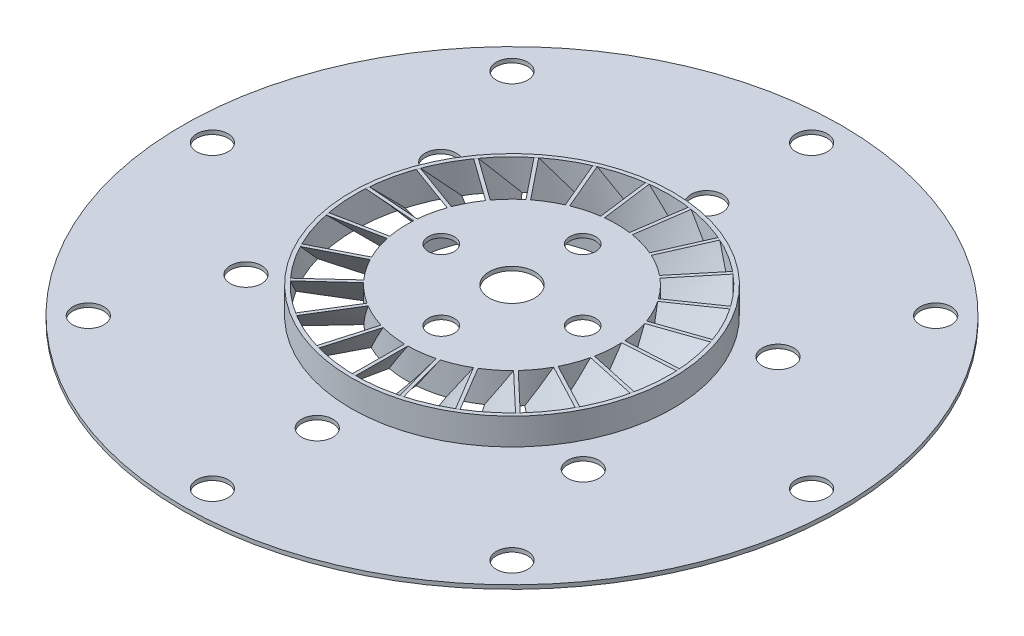
SolidWorks part; units mm, degrees
ref_plane "Front Plane" through (0, 0, 0) normal (0, 0, 1) x (1, 0, 0)
ref_plane "Top Plane" through (0, 0, 0) normal (0, 1, 0) x (1, 0, 0)
ref_plane "Right Plane" through (0, 0, 0) normal (1, 0, 0) x (0, 0, -1)
sketch "Sketch1" plane through (0, 0, 0) normal (0, 1, 0) x (1, 0, 0)
  circle A0 centre (0, 0) radius 33.25
  circle A1 centre (0, 0) radius 34.0882
  circle A2 centre (0, 0) radius 69.85
  circle A3 centre (0, 0) radius 22.25
  circle A4 centre (0, 0) radius 21.4118
  dimension "D1" = 66.5
  dimension "D2" = 0.8382
  dimension "D3" = 139.7
  dimension "D4" = 44.5
  dimension "D5" = 0.8382
extrude "Boss-Extrude1" add sketch "Sketch1" along normal blind 6.5 contours A1 A0 region at (-33.9918, 0, 0)
extrude "Boss-Extrude2" add sketch "Sketch1<3>" along normal blind 0.8382 contours A2 A1 region at (-67.8743, 0, 0)
sketch "Sketch1<3>" plane through (0, 0, 0) normal (0, 1, 0) x (1, 0, 0) same geometry as "Sketch1"
extrude "Boss-Extrude3" add sketch "Sketch1<4>" along normal blind 6.5 separate body contours A3 A4 region at (-21.6207, 0, 0)
sketch "Sketch1<4>" plane through (0, 0, 0) normal (0, 1, 0) x (1, 0, 0) same geometry as "Sketch1"
extrude "Boss-Extrude4" add sketch "Sketch1<5>" along normal blind 0.7 contours A4 region at (0, 0, 0)
sketch "Sketch1<5>" plane through (0, 0, 0) normal (0, 1, 0) x (1, 0, 0) same geometry as "Sketch1"
sketch "Sketch2" plane through (0, 0, 0) normal (0, -1, 0) x (1, 0, 0)
  line L0 (-31.9208, 9.3073) -> (-21.3278, 6.3393)
  line L1 (-33.2482, 0.35) -> (-22.2472, 0.35)
  line L2 (-33.2482, -0.35) -> (-22.2472, -0.35)
  line L3 (-32.1097, 8.6332) -> (-21.5167, 5.6652)
  line L4 (-28.226, 17.5743) -> (-18.8266, 11.8584)
  line L5 (-28.5897, 16.9762) -> (-19.1903, 11.2603)
  line L6 (-22.4378, 24.5378) -> (-14.9291, 16.498)
  line L7 (-22.9494, 24.0601) -> (-15.4407, 16.0202)
  line L8 (-14.9856, 29.6816) -> (-9.9244, 19.914)
  line L9 (-15.6071, 29.3595) -> (-10.5459, 19.592)
  line L10 (-6.4219, 32.624) -> (-4.1837, 21.8531)
  line L11 (-7.1072, 32.4815) -> (-4.869, 21.7107)
  line L12 (2.6181, 33.1468) -> (1.8674, 22.1715)
  line L13 (1.9198, 33.1945) -> (1.169, 22.2193)
  line L14 (11.4639, 31.2112) -> (7.7799, 20.8455)
  line L15 (10.8043, 31.4456) -> (7.1204, 21.0799)
  line L16 (19.4595, 26.9609) -> (13.1155, 17.9735)
  line L17 (18.8876, 27.3646) -> (12.5436, 18.3772)
  line L18 (26.0119, 20.711) -> (17.4783, 13.7685)
  line L19 (25.5701, 21.254) -> (17.0366, 14.3115)
  line L20 (30.635, 12.9251) -> (20.5449, 8.5423)
  line L21 (30.3561, 13.5671) -> (20.266, 9.1844)
  line L22 (32.9861, 4.1806) -> (22.0877, 2.6826)
  line L23 (32.8908, 4.874) -> (21.9924, 3.3761)
  line L24 (32.8908, -4.874) -> (21.9924, -3.3761)
  line L25 (32.9861, -4.1806) -> (22.0877, -2.6826)
  line L26 (30.3561, -13.5671) -> (20.266, -9.1844)
  line L27 (30.635, -12.9251) -> (20.5449, -8.5423)
  line L28 (25.5701, -21.254) -> (17.0366, -14.3115)
  line L29 (26.0119, -20.711) -> (17.4783, -13.7685)
  line L30 (18.8876, -27.3646) -> (12.5436, -18.3772)
  line L31 (19.4595, -26.9609) -> (13.1155, -17.9735)
  line L32 (10.8043, -31.4456) -> (7.1204, -21.0799)
  line L33 (11.4639, -31.2112) -> (7.7799, -20.8455)
  line L34 (1.9198, -33.1945) -> (1.169, -22.2193)
  line L35 (2.6181, -33.1468) -> (1.8674, -22.1715)
  line L36 (-7.1072, -32.4815) -> (-4.869, -21.7107)
  line L37 (-6.4219, -32.624) -> (-4.1837, -21.8531)
  line L38 (-15.6071, -29.3595) -> (-10.5459, -19.592)
  line L39 (-14.9856, -29.6816) -> (-9.9244, -19.914)
  line L40 (-22.9494, -24.0601) -> (-15.4407, -16.0202)
  line L41 (-22.4378, -24.5378) -> (-14.9291, -16.498)
  line L42 (-28.5897, -16.9762) -> (-19.1903, -11.2603)
  line L43 (-28.226, -17.5743) -> (-18.8266, -11.8584)
  line L44 (-32.1097, -8.6332) -> (-21.5167, -5.6652)
  line L45 (-31.9208, -9.3073) -> (-21.3278, -6.3393)
  circle A0 centre (0, 0) radius 33.25 construction
  circle A1 centre (0, 0) radius 22.25
  arc A2 (-21.3278, 6.3393) -> (-21.5167, 5.6652) centre (0, 0) ccw
  arc A3 (-18.8266, 11.8584) -> (-19.1903, 11.2603) centre (0, 0) ccw
  circle A5 centre (0, 0) radius 22.25 construction
  arc A6 (-31.9208, 9.3073) -> (-32.1097, 8.6332) centre (0, 0) ccw
  arc A7 (-28.226, 17.5743) -> (-28.5897, 16.9762) centre (0, 0) ccw
  arc A8 (-22.4378, 24.5378) -> (-22.9494, 24.0601) centre (0, 0) ccw
  arc A9 (-14.9291, 16.498) -> (-15.4407, 16.0202) centre (0, 0) ccw
  arc A10 (-9.9244, 19.914) -> (-10.5459, 19.592) centre (0, 0) ccw
  arc A11 (-14.9856, 29.6816) -> (-15.6071, 29.3595) centre (0, 0) ccw
  arc A12 (-6.4219, 32.624) -> (-7.1072, 32.4815) centre (0, 0) ccw
  arc A13 (-4.1837, 21.8531) -> (-4.869, 21.7107) centre (0, 0) ccw
  arc A14 (1.8674, 22.1715) -> (1.169, 22.2193) centre (0, 0) ccw
  arc A15 (2.6181, 33.1468) -> (1.9198, 33.1945) centre (0, 0) ccw
  arc A16 (11.4639, 31.2112) -> (10.8043, 31.4456) centre (0, 0) ccw
  arc A17 (7.7799, 20.8455) -> (7.1204, 21.0799) centre (0, 0) ccw
  arc A18 (13.1155, 17.9735) -> (12.5436, 18.3772) centre (0, 0) ccw
  arc A19 (19.4595, 26.9609) -> (18.8876, 27.3646) centre (0, 0) ccw
  arc A20 (26.0119, 20.711) -> (25.5701, 21.254) centre (0, 0) ccw
  arc A21 (17.4783, 13.7685) -> (17.0366, 14.3115) centre (0, 0) ccw
  arc A22 (20.5449, 8.5423) -> (20.266, 9.1844) centre (0, 0) ccw
  arc A23 (30.635, 12.9251) -> (30.3561, 13.5671) centre (0, 0) ccw
  arc A24 (32.9861, 4.1806) -> (32.8908, 4.874) centre (0, 0) ccw
  arc A25 (22.0877, 2.6826) -> (21.9924, 3.3761) centre (0, 0) ccw
  arc A26 (21.9924, -3.3761) -> (22.0877, -2.6826) centre (0, 0) ccw
  arc A27 (32.8908, -4.874) -> (32.9861, -4.1806) centre (0, 0) ccw
  arc A28 (-22.2472, 0.35) -> (-22.2472, -0.35) centre (0, 0) ccw
  arc A29 (-33.2482, 0.35) -> (-33.2482, -0.35) centre (0, 0) ccw
  arc A30 (-21.5167, -5.6652) -> (-21.3278, -6.3393) centre (0, 0) ccw
  arc A31 (-32.1097, -8.6332) -> (-31.9208, -9.3073) centre (0, 0) ccw
  arc A32 (-19.1903, -11.2603) -> (-18.8266, -11.8584) centre (0, 0) ccw
  arc A33 (-28.5897, -16.9762) -> (-28.226, -17.5743) centre (0, 0) ccw
  arc A34 (-22.9494, -24.0601) -> (-22.4378, -24.5378) centre (0, 0) ccw
  arc A35 (-15.4407, -16.0202) -> (-14.9291, -16.498) centre (0, 0) ccw
  arc A36 (-10.5459, -19.592) -> (-9.9244, -19.914) centre (0, 0) ccw
  arc A37 (-15.6071, -29.3595) -> (-14.9856, -29.6816) centre (0, 0) ccw
  arc A38 (-7.1072, -32.4815) -> (-6.4219, -32.624) centre (0, 0) ccw
  arc A39 (-4.869, -21.7107) -> (-4.1837, -21.8531) centre (0, 0) ccw
  arc A40 (1.169, -22.2193) -> (1.8674, -22.1715) centre (0, 0) ccw
  arc A41 (1.9198, -33.1945) -> (2.6181, -33.1468) centre (0, 0) ccw
  arc A42 (10.8043, -31.4456) -> (11.4639, -31.2112) centre (0, 0) ccw
  arc A43 (7.1204, -21.0799) -> (7.7799, -20.8455) centre (0, 0) ccw
  arc A44 (12.5436, -18.3772) -> (13.1155, -17.9735) centre (0, 0) ccw
  arc A45 (18.8876, -27.3646) -> (19.4595, -26.9609) centre (0, 0) ccw
  arc A46 (25.5701, -21.254) -> (26.0119, -20.711) centre (0, 0) ccw
  arc A47 (17.0366, -14.3115) -> (17.4783, -13.7685) centre (0, 0) ccw
  arc A48 (20.266, -9.1844) -> (20.5449, -8.5423) centre (0, 0) ccw
  arc A49 (30.3561, -13.5671) -> (30.635, -12.9251) centre (0, 0) ccw
  point P106 (0, 0)
  dimension "D3" = 0.7
  dimension "D1" = 0
  dimension "D4" = 23
sketch "Sketch3" plane through (0, 6.5, 0) normal (0, 1, 0) x (1, 0, 0)
  line L0 (0, 0) -> (-32.6054, -6.5152) construction
  line L1 (0, 0) -> (-15.6581, 0) construction
  line L2 (-21.8846, -4.016) -> (-32.6722, -6.1716)
  line L3 (-21.7474, -4.7025) -> (-32.535, -6.8581)
  line L4 (-22.1565, 2.0373) -> (-33.1257, 2.8721)
  line L5 (-22.2097, 1.3393) -> (-33.1788, 2.1741)
  line L6 (-20.7853, 7.9395) -> (-31.1225, 11.7028)
  line L7 (-21.0247, 7.2817) -> (-31.3619, 11.045)
  line L8 (-17.8724, 13.2529) -> (-26.811, 19.6656)
  line L9 (-18.2805, 12.6841) -> (-27.219, 19.0968)
  line L10 (-13.6341, 17.5833) -> (-20.511, 26.1698)
  line L11 (-14.1805, 17.1457) -> (-21.0574, 25.7322)
  line L12 (-8.3846, 20.6097) -> (-12.6899, 30.7332)
  line L13 (-9.0288, 20.3358) -> (-13.3341, 30.4592)
  line L14 (-2.5132, 22.1076) -> (-3.9276, 33.0172)
  line L15 (-3.2074, 22.0176) -> (-4.6218, 32.9272)
  line L16 (3.5445, 21.9659) -> (5.126, 32.8525)
  line L17 (2.8518, 22.0665) -> (4.4332, 32.9531)
  line L18 (9.3394, 20.195) -> (13.7994, 30.2513)
  line L19 (8.6995, 20.4788) -> (13.1595, 30.5351)
  line L20 (14.4416, 16.9264) -> (21.4494, 25.4064)
  line L21 (13.902, 17.3723) -> (20.9098, 25.8524)
  line L22 (18.4728, 12.4024) -> (27.5085, 18.6773)
  line L23 (18.0735, 12.9774) -> (27.1093, 19.2523)
  line L24 (21.1339, 6.9586) -> (31.5275, 10.563)
  line L25 (20.9045, 7.6199) -> (31.2982, 11.2244)
  line L26 (22.2276, 0.9987) -> (33.2083, 1.6653)
  line L27 (22.1852, 1.6974) -> (33.1659, 2.364)
  line L28 (21.6728, -5.0353) -> (32.4261, -7.356)
  line L29 (21.8204, -4.351) -> (32.5738, -6.6717)
  line L30 (19.5106, -10.6958) -> (29.239, -15.8316)
  line L31 (19.8374, -10.0768) -> (29.5658, -15.2126)
  line L32 (15.9014, -15.563) -> (23.8835, -23.1332)
  line L33 (16.3831, -15.0551) -> (24.3652, -22.6252)
  line L34 (11.1129, -19.2761) -> (16.7565, -28.719)
  line L35 (11.7137, -18.917) -> (17.3574, -28.3599)
  line L36 (5.5001, -21.5595) -> (8.3869, -32.1749)
  line L37 (6.1756, -21.3758) -> (9.0623, -31.9912)
  line L38 (-0.5205, -22.2439) -> (-0.6048, -33.2445)
  line L39 (0.1795, -22.2493) -> (0.0952, -33.2499)
  line L40 (-6.5025, -21.2786) -> (-9.5516, -31.8485)
  line L41 (-5.83, -21.4726) -> (-8.8791, -32.0425)
  line L42 (-12.0023, -18.7352) -> (-17.7901, -28.0905)
  line L43 (-11.407, -19.1035) -> (-17.1948, -28.4588)
  line L44 (-16.6119, -14.8023) -> (-24.7091, -22.2491)
  line L45 (-16.1381, -15.3175) -> (-24.2352, -22.7644)
  line L46 (-19.9895, -9.7715) -> (-29.7956, -14.7576)
  line L47 (-19.6722, -10.3955) -> (-29.4783, -15.3816)
  circle A0 centre (0, 0) radius 33.25 construction
  circle A1 centre (0, 0) radius 22.25 construction
  arc A2 (-32.6722, -6.1716) -> (-32.535, -6.8581) centre (0, 0) ccw
  arc A3 (-21.8846, -4.016) -> (-21.7474, -4.7025) centre (0, 0) ccw
  arc A4 (-22.1565, 2.0373) -> (-22.2097, 1.3393) centre (0, 0) ccw
  arc A5 (-33.1257, 2.8721) -> (-33.1788, 2.1741) centre (0, 0) ccw
  arc A6 (-20.7853, 7.9395) -> (-21.0247, 7.2817) centre (0, 0) ccw
  arc A7 (-31.1225, 11.7028) -> (-31.3619, 11.045) centre (0, 0) ccw
  arc A8 (-17.8724, 13.2529) -> (-18.2805, 12.6841) centre (0, 0) ccw
  arc A9 (-26.811, 19.6656) -> (-27.219, 19.0968) centre (0, 0) ccw
  arc A10 (-13.6341, 17.5833) -> (-14.1805, 17.1457) centre (0, 0) ccw
  arc A11 (-20.511, 26.1698) -> (-21.0574, 25.7322) centre (0, 0) ccw
  arc A12 (-8.3846, 20.6097) -> (-9.0288, 20.3358) centre (0, 0) ccw
  arc A13 (-12.6899, 30.7332) -> (-13.3341, 30.4592) centre (0, 0) ccw
  arc A14 (-2.5132, 22.1076) -> (-3.2074, 22.0176) centre (0, 0) ccw
  arc A15 (-3.9276, 33.0172) -> (-4.6218, 32.9272) centre (0, 0) ccw
  arc A16 (3.5445, 21.9659) -> (2.8518, 22.0665) centre (0, 0) ccw
  arc A17 (5.126, 32.8525) -> (4.4332, 32.9531) centre (0, 0) ccw
  arc A18 (9.3394, 20.195) -> (8.6995, 20.4788) centre (0, 0) ccw
  arc A19 (13.7994, 30.2513) -> (13.1595, 30.5351) centre (0, 0) ccw
  arc A20 (14.4416, 16.9264) -> (13.902, 17.3723) centre (0, 0) ccw
  arc A21 (21.4494, 25.4064) -> (20.9098, 25.8524) centre (0, 0) ccw
  arc A22 (18.4728, 12.4024) -> (18.0735, 12.9774) centre (0, 0) ccw
  arc A23 (27.5085, 18.6773) -> (27.1093, 19.2523) centre (0, 0) ccw
  arc A24 (21.1339, 6.9586) -> (20.9045, 7.6199) centre (0, 0) ccw
  arc A25 (31.5275, 10.563) -> (31.2982, 11.2244) centre (0, 0) ccw
  arc A26 (22.2276, 0.9987) -> (22.1852, 1.6974) centre (0, 0) ccw
  arc A27 (33.2083, 1.6653) -> (33.1659, 2.364) centre (0, 0) ccw
  arc A28 (21.6728, -5.0353) -> (21.8204, -4.351) centre (0, 0) ccw
  arc A29 (32.4261, -7.356) -> (32.5738, -6.6717) centre (0, 0) ccw
  arc A30 (19.5106, -10.6958) -> (19.8374, -10.0768) centre (0, 0) ccw
  arc A31 (29.239, -15.8316) -> (29.5658, -15.2126) centre (0, 0) ccw
  arc A32 (15.9014, -15.563) -> (16.3831, -15.0551) centre (0, 0) ccw
  arc A33 (23.8835, -23.1332) -> (24.3652, -22.6252) centre (0, 0) ccw
  arc A34 (11.1129, -19.2761) -> (11.7137, -18.917) centre (0, 0) ccw
  arc A35 (16.7565, -28.719) -> (17.3574, -28.3599) centre (0, 0) ccw
  arc A36 (5.5001, -21.5595) -> (6.1756, -21.3758) centre (0, 0) ccw
  arc A37 (8.3869, -32.1749) -> (9.0623, -31.9912) centre (0, 0) ccw
  arc A38 (-0.5205, -22.2439) -> (0.1795, -22.2493) centre (0, 0) ccw
  arc A39 (-0.6048, -33.2445) -> (0.0952, -33.2499) centre (0, 0) ccw
  arc A40 (-6.5025, -21.2786) -> (-5.83, -21.4726) centre (0, 0) ccw
  arc A41 (-9.5516, -31.8485) -> (-8.8791, -32.0425) centre (0, 0) ccw
  arc A42 (-12.0023, -18.7352) -> (-11.407, -19.1035) centre (0, 0) ccw
  arc A43 (-17.7901, -28.0905) -> (-17.1948, -28.4588) centre (0, 0) ccw
  arc A44 (-16.6119, -14.8023) -> (-16.1381, -15.3175) centre (0, 0) ccw
  arc A45 (-24.7091, -22.2491) -> (-24.2352, -22.7644) centre (0, 0) ccw
  arc A46 (-19.9895, -9.7715) -> (-19.6722, -10.3955) centre (0, 0) ccw
  arc A47 (-29.7956, -14.7576) -> (-29.4783, -15.3816) centre (0, 0) ccw
  point P101 (0, 0)
  dimension "D1" = 11.3
  dimension "D2" = 0.35
  dimension "D3" = 0.35
  dimension "D4" = 23
loft "Loft1" add section "Sketch2" section "Sketch3" connector at (-32.1097, 0, 8.6332) connector at (-29.7956, 6.5, 14.7576)
pattern_circular "CirPattern1" count 23 over 360 about axis through (0, 6.5, 0) along (0, -1, 0) of "Loft1"
sketch "Sketch4" plane through (0, 6.5, 0) normal (0, 1, 0) x (1, 0, 0)
  circle A0 centre (0, 0) radius 21.55
  dimension "D1" = 43.1
extrude "Boss-Extrude5" add sketch "Sketch4" against normal blind 0.8382
sketch "Sketch6" plane through (0, 0, 0) normal (0, -1, 0) x (1, 0, 0)
  line L0 (0, 0) -> (0, 14.9949) construction
  line L1 (0, 0) -> (14.9949, 0) construction
  line L2 (0, 0) -> (0, -14.9949) construction
  line L3 (0, 0) -> (-14.9949, 0) construction
  point P9 (0, 0)
  dimension "D1" = 14.9949
  dimension "D2" = 4
hole_wizard "CBORE for M5 Hex Head Bolt1" positions "3DSketch4" profile "Sketch7" counterbore size "M5" standard "ANSI Metric" end condition through all
sketch3d "3DSketch4"
  point P0 (0, 0, 14.9949)
  point P3 (14.9949, 0, 0)
  point P6 (0, 0, -14.9949)
  point P9 (-14.9949, 0, 0)
sketch "Sketch7" plane through (0, 0, 14.9949) normal (1, 0, 0) x (0, 0, -1)
  line L0 (0, 0) -> (0, 6.5001)
  line L1 (0, 6.5001) -> (2.75, 6.5001)
  line L3 (2.75, 6.5001) -> (2.75, 3.58)
  line L4 (2.75, 3.58) -> (6.12, 3.58)
  line L5 (6.12, 3.58) -> (6.12, 0)
  line L7 (6.12, 0) -> (0, 0)
  line L11 (0, -6.35) -> (0, 107.95) construction
  dimension "Thru Hole Dia." = 5.5
  dimension "Thru Hole Depth" = 6.5001
  dimension "C'Bore Dia." = 12.24
  dimension "C'Bore Depth" = 3.58
sketch "Sketch8" plane through (0, 0, 0) normal (0, -1, 0) x (1, 0, 0)
  circle A0 centre (0, 0) radius 21.39
  arc A1 (22.0877, -2.6826) -> (22.0877, 2.6826) centre (0, 0) ccw construction
  circle A2 centre (0, 0) radius 22.25
  dimension "D1" = 0.86
  dimension "D2" = 44.5
extrude "Cut-Extrude1" cut sketch "Sketch8" against normal blind 1.5 contours A0 region at (0, 0, 0)
extrude "Boss-Extrude6" add sketch "Sketch8<2>" against normal up to surface (6.5 mm away) up to face at (0, 6.5, 17.7449)
sketch "Sketch8<2>" plane through (0, 0, 0) normal (0, -1, 0) x (1, 0, 0) same geometry as "Sketch8"
sketch "Sketch9" plane through (0, 5.6618, 0) normal (0, -1, 0) x (1, 0, 0)
  circle A0 centre (0, 0) radius 4.826
  dimension "D1" = 9.652
extrude "Cut-Extrude3" cut sketch "Sketch9" against normal blind 2.54
sketch "Sketch10" plane through (0, 0, 0) normal (0, -1, 0) x (1, 0, 0)
  line L0 (0, 0) -> (0, 63.5) construction
  circle A0 centre (0, 63.5) radius 3.3147
  dimension "D2" = 6.6294
  dimension "D1" = 63.5
extrude "Cut-Extrude4" cut sketch "Sketch10" against normal blind 10
pattern_circular "CirPattern2" count 8 over 360 about axis through (0, 1.5, 0) along (0, -1, 0) of "Cut-Extrude4"
sketch "Sketch11" plane through (0, 0, 0) normal (0, -1, 0) x (1, 0, 0)
  line L0 (0, 0) -> (0, 41.275) construction
  circle A0 centre (0, 41.275) radius 3.3147
  dimension "D2" = 6.6294
  dimension "D1" = 41.275
extrude "Cut-Extrude5" cut sketch "Sketch11" against normal blind 10
pattern_circular "CirPattern3" count 6 over 360 about axis through (0, 1.5, 0) along (0, -1, 0) of "Cut-Extrude5"
